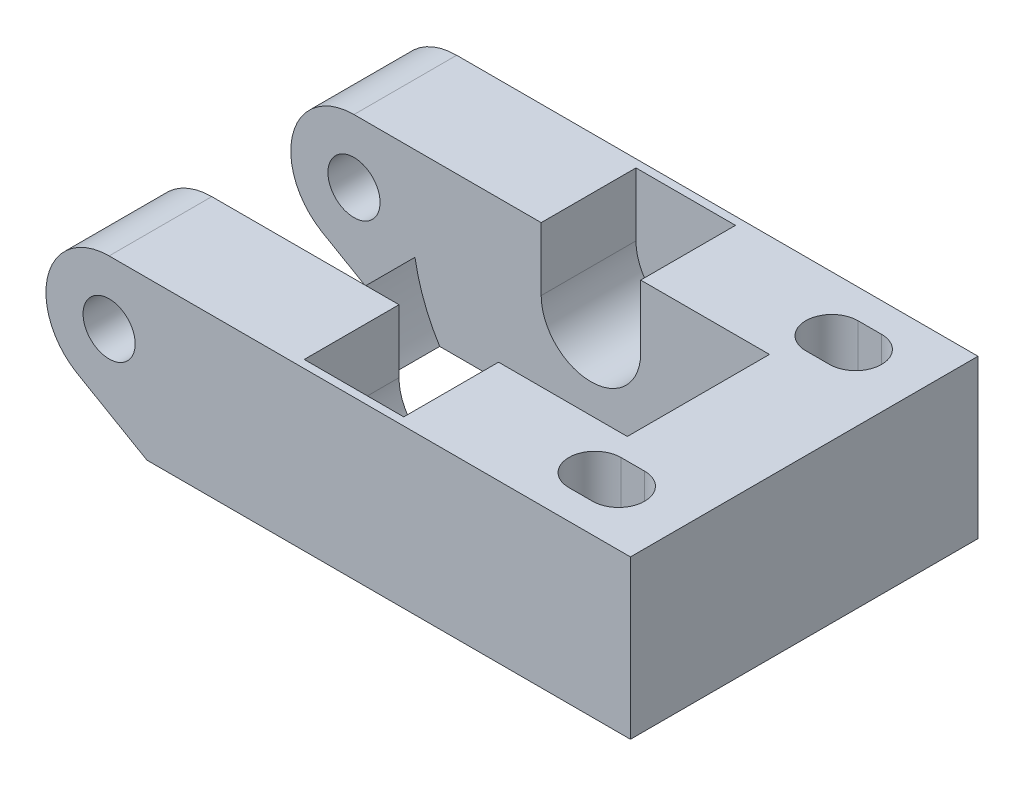
SolidWorks part; units mm, degrees
ref_plane "Front Plane" through (0, 0, 0) normal (0, 0, 1) x (1, 0, 0)
ref_plane "Top Plane" through (0, 0, 0) normal (0, 1, 0) x (1, 0, 0)
ref_plane "Right Plane" through (0, 0, 0) normal (1, 0, 0) x (0, 0, -1)
sketch "Sketch1" plane through (0, 0, 0) normal (0, 0, 1) x (1, 0, 0)
  line L0 (-17, -3.4641) -> (-12.6077, -6)
  line L1 (-12.6077, -6) -> (18, -6)
  line L3 (-15, 4) -> (18, 4)
  line L4 (18, -6) -> (18, 4)
  circle A1 centre (-15, 0) radius 1.65
  arc A2 (-15, 4) -> (-17, -3.4641) centre (-15, 0) ccw
  dimension "D2" = 4
  dimension "D3" = 3.3
  dimension "D4" = 4
  dimension "D1" = 15
  dimension "D5" = 10
  dimension "D6" = 150
  dimension "D7" = 18
extrude "Boss-Extrude1" add sketch "Sketch1" along normal blind 22
ref_plane "Plane1" through (0, 0, 11) normal (0, 0, 1) x (1, 0, 0)
sketch "Sketch2" plane through (0, 0, 11) normal (0, 0, 1) x (1, 0, 0)
  line L0 (-11.706, -2.764) -> (-19.3, -11.8142)
  line L1 (-19.3, 11.3) -> (11.3, 11.3)
  line L2 (11.3, 11.3) -> (11.3, 0)
  line L3 (-19.3, -11.8142) -> (-19.3, 11.3)
  arc A0 (-11.14, -1.8948) -> (11.3, 0) centre (0, 0) ccw
  arc A1 (-11.706, -2.764) -> (-11.14, -1.8948) centre (-15, 0) ccw
  circle A2 centre (-15, 0) radius 1.65 construction
  dimension "D1" = 22.6
  dimension "D2" = 8.6
  dimension "D3" = 40
extrude "Cut-Extrude1" cut sketch "Sketch2" against normal blind 4.5 and the other way blind 4.5
sketch "Sketch4" plane through (0, 0, 11) normal (0, 0, 1) x (1, 0, 0)
  line L0 (-3.15, 0) -> (-3.15, 6.453)
  line L1 (-3.15, 6.453) -> (3.15, 6.453)
  line L2 (3.15, 6.453) -> (3.15, 0)
  arc A0 (-3.15, 0) -> (3.15, 0) centre (0, 0) ccw
  dimension "D1" = 3.15
extrude "Cut-Extrude3" cut sketch "Sketch4" against normal blind 10.5 and the other way blind 10.5
ref_axis "Axis1" through (0, 0, 6.5) along (0, 0, -1)
sketch "Sketch3" plane through (0, -6, 0) normal (0, -1, 0) x (1, 0, 0)
  line L0 (13, 18.5) -> (13, 3.8848) construction
  line L1 (13.75, 18.5) -> (12.25, 18.5) construction
  line L2 (13.75, 16.85) -> (12.25, 16.85)
  line L3 (13.75, 20.15) -> (12.25, 20.15)
  line L4 (0, 6.5) -> (0, 0.5) construction
  line L5 (5.5, 11) -> (-5.5, 11) construction
  line L6 (15.943, 11) -> (0, 11) construction
  line L7 (13.75, 3.5) -> (12.25, 3.5) construction
  line L8 (13.75, 5.15) -> (12.25, 5.15)
  line L9 (13.75, 1.85) -> (12.25, 1.85)
  arc A0 (13.75, 16.85) -> (13.75, 20.15) centre (13.75, 18.5) ccw
  arc A1 (12.25, 20.15) -> (12.25, 16.85) centre (12.25, 18.5) ccw
  arc A2 (13.75, 5.15) -> (13.75, 1.85) centre (13.75, 3.5) cw
  arc A3 (12.25, 1.85) -> (12.25, 5.15) centre (12.25, 3.5) cw
  point P4 (13, 18.5)
  point P17 (13, 3.5)
  dimension "D2" = 1.65
  dimension "D1" = 1.5
  dimension "D3" = 13
  dimension "D4" = 7.5
extrude "Cut-Extrude2" cut sketch "Sketch3" against normal through all
